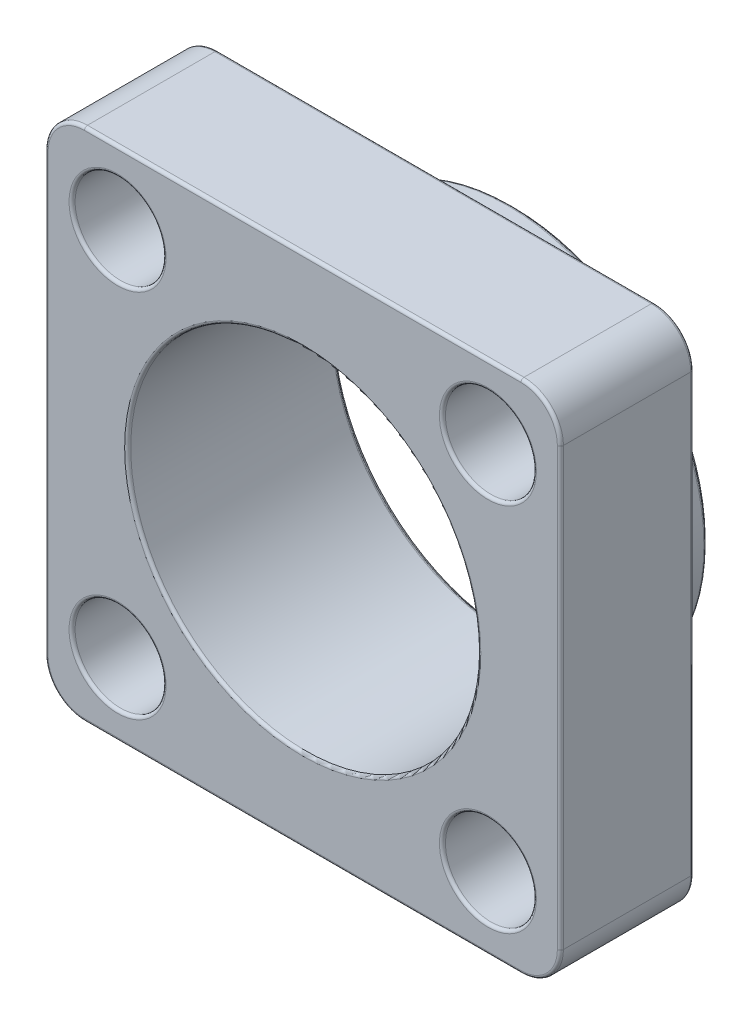
SolidWorks part; units mm, degrees
material "moto_black"
ref_plane "Front Plane" through (0, 0, 0) normal (0, 0, 1) x (1, 0, 0)
ref_plane "Top Plane" through (0, 0, 0) normal (0, 1, 0) x (1, 0, 0)
ref_plane "Right Plane" through (0, 0, 0) normal (1, 0, 0) x (0, 0, -1)
sketch "Sketch1" plane through (0, 0, 0) normal (0, 0, 1) x (1, 0, 0)
  line L0 (0, 0) -> (0, -27.5504)
  line L1 (-72, -85) -> (72, -85)
  line L2 (-85, -72) -> (-85, 72)
  line L3 (-72, 85) -> (72, 85)
  line L4 (85, -72) -> (85, 72)
  line L5 (-85, -85) -> (85, 85) construction
  line L6 (-85, 85) -> (85, -85) construction
  line L7 (0, -27.5504) -> (0, 0)
  line L8 (0, 0) -> (23.1269, 0)
  arc A0 (-72, -85) -> (-85, -72) centre (-72, -72) cw
  arc A1 (72, -85) -> (85, -72) centre (72, -72) ccw
  arc A2 (72, 85) -> (85, 72) centre (72, 72) cw
  arc A3 (-85, 72) -> (-72, 85) centre (-72, 72) cw
  circle A4 centre (0, 0) radius 57.75
  circle A5 centre (-61.0879, 61.0879) radius 15
  circle A6 centre (61.0879, 61.0879) radius 15
  circle A7 centre (61.0879, -61.0879) radius 15
  circle A8 centre (-61.0879, -61.0879) radius 15
  point P0 (0, 0)
  dimension "D3" = 13
  dimension "D4" = 115.5
  dimension "D5" = 30
  dimension "D1" = 170
  dimension "D2" = 170
extrude "Boss-Extrude1" add sketch "Sketch1" along normal mid plane 40 contours A3 L2 A0 L1 A1 L4 A2 L3 A6 A5 A4 A7 A8 region at (-79.4924, -79.4924, 0)
sketch "Sketch2" plane through (0, 0, -20) normal (0, 0, -1) x (-1, 0, 0)
  line L0 (-85, 72) -> (-85, -72)
  line L1 (-72, -85) -> (72, -85)
  line L2 (85, -72) -> (85, 72)
  line L3 (72, 85) -> (-72, 85)
  line L8 (79, -72) -> (79, 72)
  line L9 (-72, -79) -> (72, -79)
  line L10 (-79, 72) -> (-79, -72)
  line L11 (72, 79) -> (-72, 79)
  line L12 (79, -72) -> (79, 72)
  line L13 (-72, -79) -> (72, -79)
  line L14 (-79, 72) -> (-79, -72)
  line L15 (72, 79) -> (-72, 79)
  arc A0 (-72, 85) -> (-85, 72) centre (-72, 72) ccw
  arc A1 (-85, -72) -> (-72, -85) centre (-72, -72) ccw
  circle A2 centre (0, 0) radius 64.75
  circle A3 centre (0, 0) radius 64.75
  arc A4 (72, -85) -> (85, -72) centre (72, -72) ccw
  arc A5 (85, 72) -> (72, 85) centre (72, 72) ccw
  circle A6 centre (0, 0) radius 57.75
  arc A10 (79, 72) -> (72, 79) centre (72, 72) ccw
  arc A11 (72, -79) -> (79, -72) centre (72, -72) ccw
  arc A12 (-79, -72) -> (-72, -79) centre (-72, -72) ccw
  arc A13 (-72, 79) -> (-79, 72) centre (-72, 72) ccw
  arc A14 (79, 72) -> (72, 79) centre (72, 72) ccw
  arc A15 (72, -79) -> (79, -72) centre (72, -72) ccw
  arc A16 (-79, -72) -> (-72, -79) centre (-72, -72) ccw
  arc A17 (-72, 79) -> (-79, 72) centre (-72, 72) ccw
  circle M21 centre (0, 0) radius 57.75
  arc M22 (85, 72) -> (72, 85) centre (72, 72) ccw
  line M23 (72, 85) -> (-72, 85)
  arc M24 (-72, 85) -> (-85, 72) centre (-72, 72) ccw
  line M25 (-85, 72) -> (-85, -72)
  arc M26 (-85, -72) -> (-72, -85) centre (-72, -72) ccw
  line M27 (-72, -85) -> (72, -85)
  arc M28 (72, -85) -> (85, -72) centre (72, -72) ccw
  line M29 (85, -72) -> (85, 72)
  dimension "D1" = 7
  dimension "D2" = 6
  dimension "D3" = 6
  dimension "D4" = 7
extrude "Boss-Extrude4" add sketch "Sketch2" along normal blind 4 contours A17 L15 A14 L12 A15 L13 A16 L14 M29 M22 M23 M24 M25 M26 M27 M28 region at (79.4924, 79.4924, -20)
extrude "Boss-Extrude5" add sketch "Sketch2<5>" along normal blind 15 contours A3 M21 region at (62.9186, 0, -20)
sketch "Sketch2<5>" plane through (0, 0, -20) normal (0, 0, -1) x (-1, 0, 0) same geometry as "Sketch2"
sketch "Sketch3" plane through (0, 0, -35) normal (0, 0, -1) x (-1, 0, 0)
  circle A1 centre (0, 0) radius 69.049
  circle A2 centre (0, 0) radius 57.75
extrude "Boss-Extrude6" add sketch "Sketch3" along normal blind 4
sketch "Sketch4" plane through (0, 0, -39) normal (0, 0, -1) x (-1, 0, 0)
  circle A0 centre (0, 0) radius 64.75
  circle A1 centre (0, 0) radius 57.75
extrude "Boss-Extrude7" add sketch "Sketch4" along normal blind 11
fillet "Fillet2" radius 1 1 edges at (64.75, 0, -20)
fillet "Fillet3" radius 1 10 edges at (-76.9497, 76.9497, -20) (-79, 0, -20) (-76.9497, -76.9497, -20) (0, -79, -20) (76.9497, -76.9497, -20) (79, 0, -20) (76.9497, 76.9497, -20) (0, 79, -20) (-64.75, 0, -35) (-64.75, 0, -39)
fillet "Fillet4" radius 1 2 edges at (-69.049, 0, -35) (-69.049, 0, -39)
chamfer "Chamfer1" distance 2 angle 45 2 edges at (-57.75, 0, -50) (-64.75, 0, -50)
fillet "Fillet5" radius 1 4 edges at (-57.75, 0, -48) (-64.75, 0, -48) (-59.75, 0, -50) (-62.75, 0, -50)
fillet "Fillet6" radius 1 16 edges at (-81.1924, -81.1924, -24) (0, -85, -24) (81.1924, -81.1924, -24) (85, 0, -24) (81.1924, 81.1924, -24) (0, 85, -24) (-81.1924, 81.1924, -24) (-85, 0, -24) (79, 0, -24) (76.9497, -76.9497, -24) (0, -79, -24) (-76.9497, -76.9497, -24) (-79, 0, -24) (-76.9497, 76.9497, -24) (0, 79, -24) (76.9497, 76.9497, -24)
fillet "Fillet7" radius 1 4 edges at (-46.0879, -61.0879, -20) (76.0879, -61.0879, -20) (76.0879, 61.0879, -20) (-46.0879, 61.0879, -20)
fillet "Fillet8" radius 1 13 edges at (-46.0879, -61.0879, 20) (76.0879, -61.0879, 20) (0, 85, 20) (81.1924, 81.1924, 20) (85, 0, 20) (81.1924, -81.1924, 20) (0, -85, 20) (-81.1924, -81.1924, 20) (-85, 0, 20) (-81.1924, 81.1924, 20) (57.75, 0, 20) (-46.0879, 61.0879, 20) (76.0879, 61.0879, 20)
